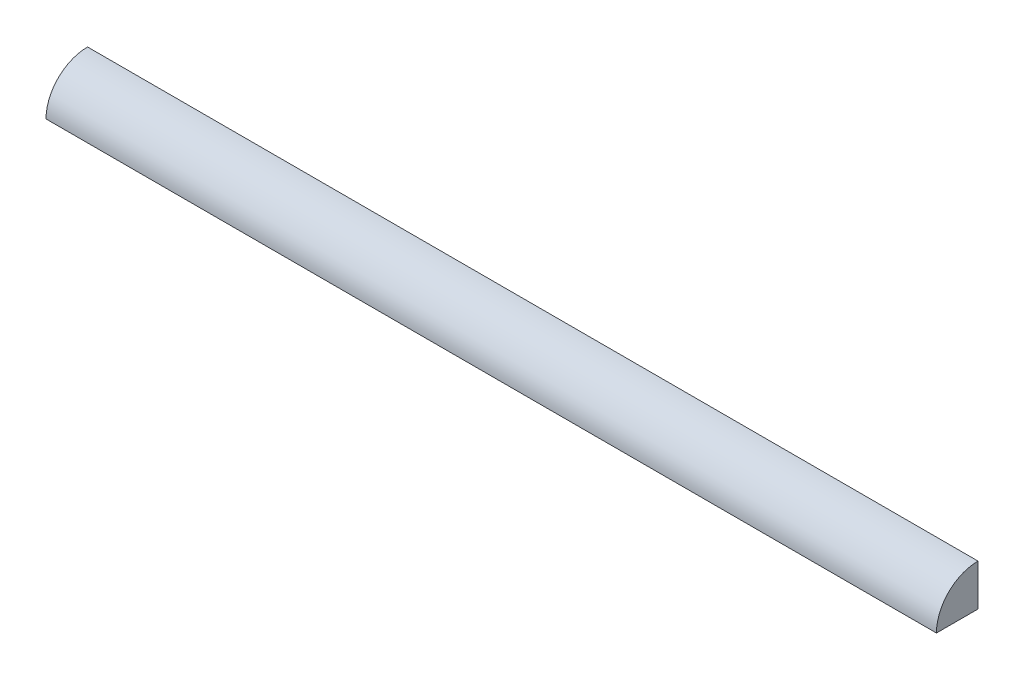
SolidWorks part; units mm, degrees
ref_plane "Plan de face" through (0, 0, 0) normal (0, 0, 1) x (1, 0, 0)
ref_plane "Plan de dessus" through (0, 0, 0) normal (0, 1, 0) x (1, 0, 0)
ref_plane "Plan de droite" through (0, 0, 0) normal (1, 0, 0) x (0, 0, -1)
sketch "Esquisse1" plane through (0, 0, 0) normal (0, 0, 1) x (1, 0, 0)
  line L1 (-111.1765, 46.7353) -> (488.8235, 46.7353)
  line L2 (-111.1765, 46.7353) -> (-111.1765, 18.7353)
  line L3 (-111.1765, 18.7353) -> (488.8235, 18.7353)
  line L4 (488.8235, 46.7353) -> (488.8235, 18.7353)
  dimension "D1" = 28
  dimension "D2" = 600
extrude "Boss.-Extru.1" add sketch "Esquisse1" along normal blind 28
fillet "Congé1" radius 28 1 edges at (188.8235, 46.7353, 28) type face fillet first side face at (188.8235, 46.7353, 14) second side face at (188.8235, 32.7353, 28)
